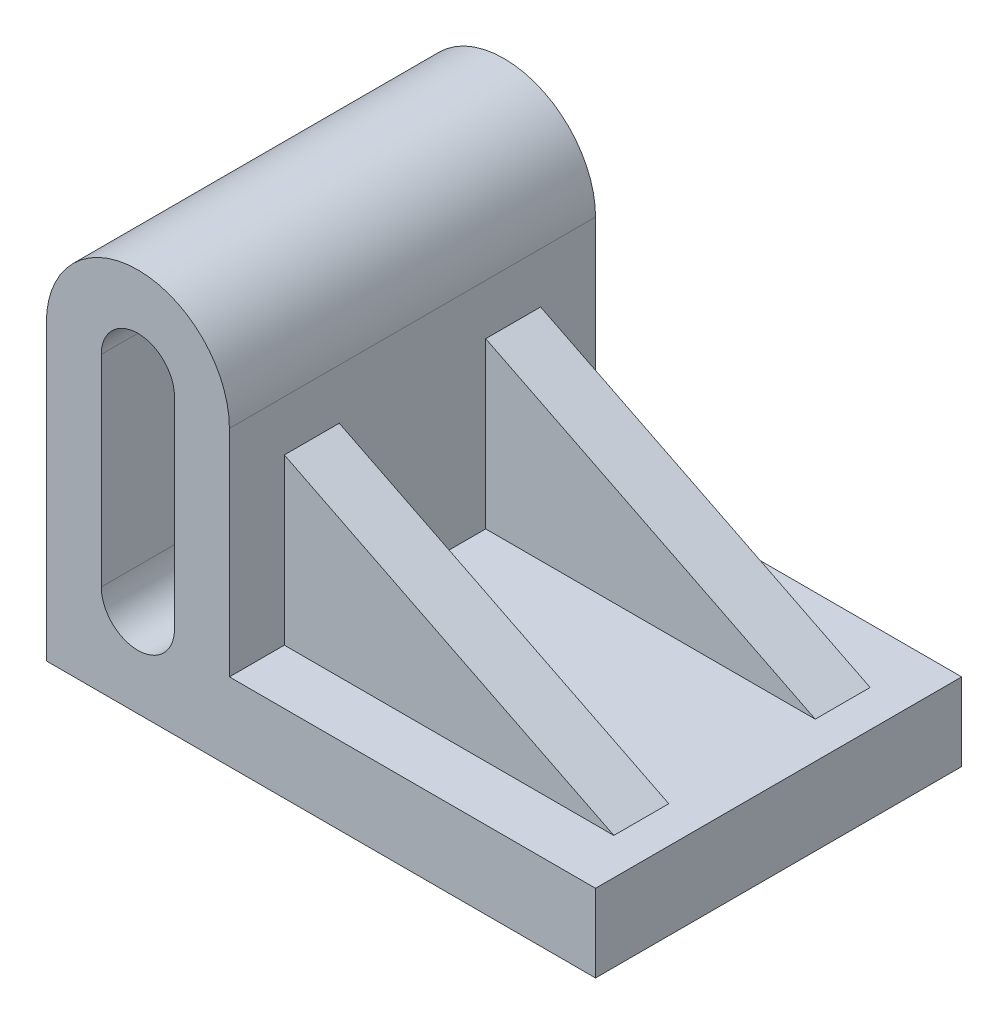
SolidWorks part; units mm, degrees
ref_plane "Front Plane" through (0, 0, 0) normal (0, 0, 1) x (1, 0, 0)
ref_plane "Top Plane" through (0, 0, 0) normal (0, 1, 0) x (1, 0, 0)
ref_plane "Right Plane" through (0, 0, 0) normal (1, 0, 0) x (0, 0, -1)
sketch "Sketch1" plane through (0, 0, 0) normal (0, 0, 1) x (1, 0, 0)
  line L0 (0, 0) -> (150, 0)
  line L1 (0, 0) -> (0, 80)
  line L2 (150, 0) -> (150, 21.2228)
  line L3 (150, 21.2228) -> (50, 21.2228)
  line L4 (50, 21.2228) -> (50, 80)
  arc A0 (50, 80) -> (0, 80) centre (25, 80) ccw
  dimension "D3" = 50
  dimension "D1" = 150
  dimension "D2" = 80
extrude "Boss-Extrude2" add sketch "Sketch1" against normal blind 50 and the other way blind 50
sketch "Sketch7" plane through (0, 0, 50) normal (0, 0, 1) x (1, 0, 0)
  line L0 (25, 80) -> (25, 25) construction
  line L1 (35, 80) -> (35, 25)
  line L2 (15, 80) -> (15, 25)
  line L4 (0, 0) -> (150, 0) construction
  arc A0 (35, 80) -> (15, 80) centre (25, 80) ccw
  arc A1 (15, 25) -> (35, 25) centre (25, 25) ccw
  point P2 (25, 52.5)
  point P7 (0, 0)
  point P9 (0, 0)
  dimension "D1" = 10
  dimension "D3" = 25
  dimension "D4" = 80
extrude "Cut-Extrude2" cut sketch "Sketch7" against normal through all
sketch "Sketch9" plane through (0, 0, 0) normal (0, 0, 1) x (1, 0, 0)
  line L0 (50, 66.2228) -> (50, 21.2228)
  line L1 (50, 21.2228) -> (140, 21.2228)
  line L2 (140, 21.2228) -> (50, 66.2228)
  line L3 (150, 21.2228) -> (50, 21.2228) construction
  line L4 (50, 21.2228) -> (50, 80) construction
  line L5 (150, 0) -> (150, 21.2228) construction
  dimension "D1" = 10
  dimension "D2" = 45
extrude "Boss-Extrude3" add sketch "Sketch9" along normal blind 35 and the other way blind 35
sketch "Sketch10" plane through (0, 21.2228, 0) normal (0, 1, 0) x (1, 0, 0)
  line L0 (50, 35) -> (50, -35) construction
  line L1 (50, 20) -> (149.0449, 20)
  line L2 (50, 20) -> (50, -20)
  line L3 (50, -20) -> (149.0449, -20)
  line L4 (149.0449, 20) -> (149.0449, -20)
  line L5 (-57.75, 0) -> (57.75, 0) construction
  dimension "D1" = 40
  dimension "D2" = 20
extrude "Cut-Extrude3" cut sketch "Sketch10" along normal through all
